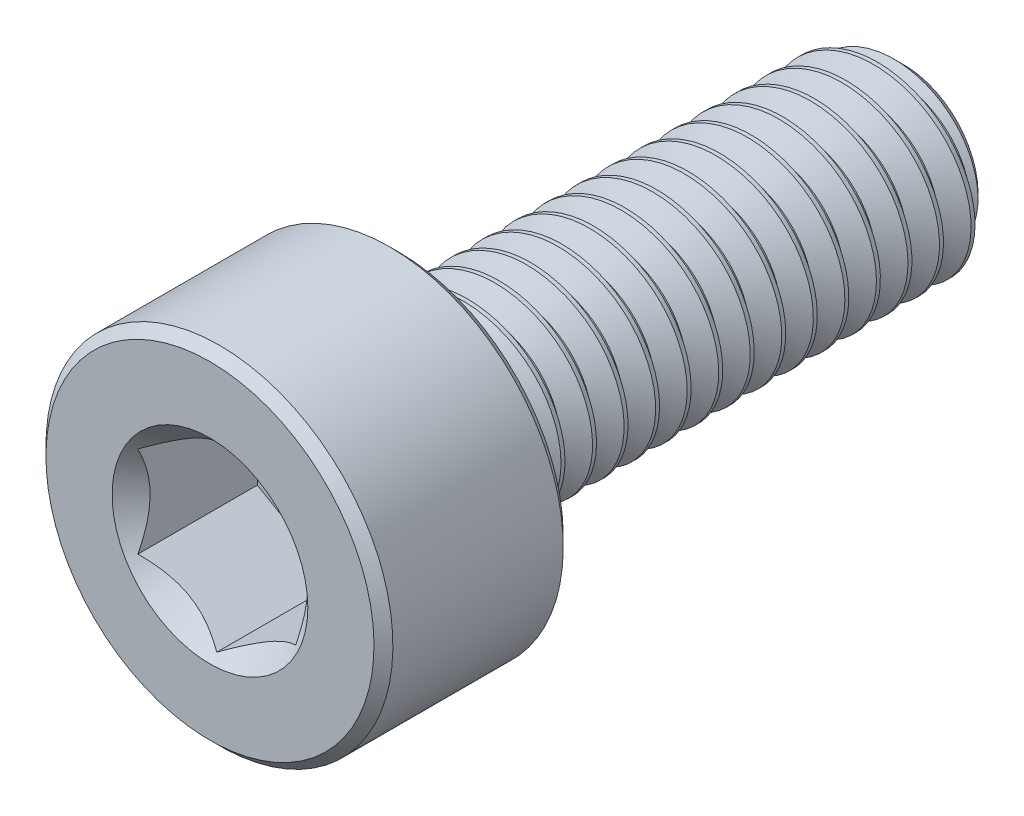
SolidWorks part; units mm, degrees
ref_plane "Front Plane" through (0, 0, 0) normal (0, 0, 1) x (1, 0, 0)
ref_plane "Top Plane" through (0, 0, 0) normal (0, 1, 0) x (1, 0, 0)
ref_plane "Right Plane" through (0, 0, 0) normal (1, 0, 0) x (0, 0, -1)
sketch "Sketch1" plane through (0, 0, 0) normal (1, 0, 0) x (0, 0, -1)
  line L0 (-5.5, 0) -> (5.5, 0) construction
  line L1 (5.5, 0) -> (5.5, 1.1752) construction
  line L2 (5.5, 1.1752) -> (5.1752, 1.5) construction
  line L3 (5.1752, 1.5) -> (5.125, 1.5) construction
  line L4 (5.125, 1.5) -> (-2.5, 1.5) construction
  line L5 (-2.5, 1.5) -> (-2.5, 2.75) construction
  line L6 (-2.5, 2.75) -> (-5.5, 2.75) construction
  line L7 (-5.5, 2.75) -> (-5.5, 0) construction
  line L8 (5.5, 1.1752) -> (5.5, 1.5) construction
  line L9 (5.4687, 1.5541) -> (5.7187, 1.1211) construction
  line L10 (5.7187, 1.1211) -> (5.9687, 1.5541) construction
  line L11 (5.9687, 1.5541) -> (5.4687, 1.5541) construction
  line L12 (5.7187, 1.5541) -> (5.7187, 1.5) construction
  line L13 (5.7187, 1.1211) -> (5.7187, 1.1752) construction
  line L14 (5.6875, 1.1752) -> (5.75, 1.1752) construction
  line L15 (5.5, 1.5) -> (5.9375, 1.5) construction
  line L16 (5.4844, 1.5271) -> (5.9531, 1.5271) construction
  line L17 (5.5, 0) -> (5.5, -1.5) construction
  line L18 (-2.65, 2.75) -> (-2.5, 2.6) construction
  line L19 (-5.35, 2.75) -> (-5.5, 2.6) construction
  line L20 (-2.5, 1.5) -> (-2.5, 0) construction
  line L21 (-2.5, 0.75) -> (0.1667, 0.75) construction
  line L22 (0.1667, 0.75) -> (2.8333, 0.75) construction
  line L23 (2.8333, 0.75) -> (5.5, 0.75) construction
  line L24 (0.1667, 0.75) -> (0.1667, 1.5) construction
  line L25 (0.1667, 1.5) -> (0.1667, 2.75) construction
  line L26 (2.8333, 0.75) -> (2.8333, 2.75) construction
  point P0 (-5.5, 1.25)
  point P3 (4.25, 1.5)
  point P4 (0, 0)
  point P18 (2.8333, 1.5)
  point P22 (5.7187, 1.1752)
  point P24 (5.125, 1.5)
  point P25 (5.7187, 1.5)
  point P28 (5.7187, 1.5271)
  point P29 (4.25, -1.5)
  point P30 (0.1667, 1.5)
  point P31 (-4, 2.75)
  point P37 (-3.025, 2.75)
  point P38 (-5.275, 2.75)
  point P45 (0.1667, 0.75)
  point P46 (2.8333, 0.75)
  dimension "D2" = 0.0625
  dimension "D7" = 0.15
  dimension "D8" = 0.15
  dimension "D9" = 0.15
  dimension "D10" = 0.075
  dimension "D11" = 0.375
  dimension "Drive Size" = 2.5
  dimension "Head Diameter" = 5.5
  dimension "Head Height" = 3
  dimension "Thread Pitch" = 0.5
  dimension "Thread Dia" = 3
  dimension "Length" = 8
  dimension "D12" = 0.375
  dimension "D4" = 1.25
  dimension "D3" = 45
sketch "Sketch2" plane through (0, 0, 0) normal (1, 0, 0) x (0, 0, -1)
  line L0 (-5.5, 0) -> (-5.5, 2.6)
  line L1 (-5.35, 2.75) -> (-2.65, 2.75)
  line L2 (-2.5, 2.6) -> (-2.5, 1.65)
  line L4 (5.1752, 1.5) -> (5.5, 1.1752)
  line L5 (5.5, 1.1752) -> (5.5, 0)
  line L6 (-2.5, 2.75) -> (-5.5, 2.75) construction
  line L7 (5.5, 0) -> (-5.5, 0)
  line L8 (-5.35, 2.75) -> (-5.5, 2.6) construction
  line L10 (-5.35, 2.75) -> (-5.5, 2.6)
  line L14 (-2.65, 2.75) -> (-2.5, 2.6) construction
  line L16 (-2.65, 2.75) -> (-2.5, 2.6)
  line L17 (-2.5, 1.5) -> (-2.5, 2.75) construction
  line L19 (-2.35, 1.5) -> (5.1752, 1.5)
  line L20 (5.125, 1.5) -> (-2.5, 1.5) construction
  arc A1 (-2.5, 1.65) -> (-2.35, 1.5) centre (-2.35, 1.65) ccw
  dimension "D3" = 0.15
revolve "Revolve1" add sketch "Sketch2" angle 360 about L7
sketch "Sketch3" plane through (0, 0, 5.5) normal (0, 0, 1) x (1, 0, 0)
  line L1 (1.25, -0.7217) -> (1.25, 0.7217)
  line L2 (1.25, 0.7217) -> (0, 1.4434)
  line L3 (0, 1.4434) -> (-1.25, 0.7217)
  line L4 (-1.25, 0.7217) -> (-1.25, -0.7217)
  line L5 (-1.25, -0.7217) -> (0, -1.4434)
  line L6 (0, -1.4434) -> (1.25, -0.7217)
  circle A0 centre (0, 0) radius 1.25 construction
  circle A1 centre (0, 0) radius 2.75 construction
  circle A2 centre (0, 0) radius 2.75 construction
  circle A3 centre (0, 0) radius 1.4434 construction
  point P13 (0, 0)
  dimension "D1" = 2.8868
extrude "Cut-Extrude1" cut sketch "Sketch3" against normal offset from surface (2 mm away) 1 up to face at (0, 2.6, 2.5)
sketch "Sketch4" plane through (0, 0, 5.5) normal (0, 0, 1) x (1, 0, 0)
  circle A0 centre (0, 0) radius 1.5516
  dimension "D1" = 3.1033
extrude "Cut-Extrude2" cut sketch "Sketch4" against normal up to vertex (1.5 mm away) draft 45 up to point (0, 2.75, 4)
sketch "Sketch11" plane through (0, 0, 0) normal (1, 0, 0) x (0, 0, -1)
  line L0 (-5.5, 0) -> (5.5, 0) construction
  line L1 (-5.5, 0) -> (5.5, 0) construction
  line L2 (-1, 0) -> (-1, 1.5) construction
  line L3 (5.125, 1.5) -> (-2.5, 1.5) construction
  line L4 (4, 0) -> (4, 1.5) construction
  line L6 (5.5, 1.1752) -> (5.5, 1.5) construction
  point P2 (-1, 0)
  point P3 (4, 0)
  dimension "D1" = 1.5
  dimension "D2" = 1.5
sketch "Sketch6" plane through (0, 0, -5.5) normal (0, 0, -1) x (-1, 0, 0)
  circle A0 centre (0, 0) radius 1.5
curve "Helix/Spiral1" pitch 0.5 height 8.5 turns 17
sketch "Sketch10" plane through (0, 0, 0) normal (1, 0, 0) x (0, 0, -1)
  line L0 (-2.35, -2.75) -> (-2.35, 2.75)
  line L5 (-5.5, 0) -> (5.5, 0) construction
  line L6 (-2.35, 1.5) -> (-2.35, -1.5) construction
  point P3 (-2.35, 0)
split "Split1" trim tools "Sketch10" bodies to split 106 resulting bodies 114 115
sketch "Sketch7" plane through (0, 0, 0) normal (1, 0, 0) x (0, 0, -1)
  line L0 (5.4844, 1.5271) -> (5.9531, 1.5271)
  line L1 (5.9531, 1.5271) -> (5.75, 1.1752)
  line L2 (5.75, 1.1752) -> (5.6875, 1.1752)
  line L3 (5.6875, 1.1752) -> (5.4844, 1.5271)
sweep "Cut-Sweep1" cut profiles "Sketch7" path "Helix/Spiral1" align with end faces yes
sketch "Sketch8" plane through (0, 0, 0) normal (1, 0, 0) x (0, 0, -1)
  line L0 (-2.5, 0) -> (-2.5, 1.5)
  line L1 (-2.35, -1.5) -> (-2.35, 1.5) construction
  line L2 (-2.5, 1.5) -> (-2.35, 1.5)
  line L4 (-2.35, 1.5) -> (-1.484, 0)
  line L5 (-1.484, 0) -> (-2.5, 0)
  line L6 (5.125, 1.5) -> (-2.5, 1.5) construction
  line L7 (-5.5, 0) -> (5.5, 0) construction
  dimension "D1" = 60
revolve "Revolve2" add sketch "Sketch8" angle 360 about L5
equation "\"D2@Sketch1\" = \"Thread Pitch@Sketch1\" / 8"
equation "\"D4@Helix/Spiral1\" = \"Thread Pitch@Sketch1\""
equation "\"D7@Sketch1\" = \"Head Height@Sketch1\" * .05"
equation "\"D8@Sketch1\"=\"D7@Sketch1\""
equation "\"D9@Sketch1\"=\"D7@Sketch1\""
equation "\"D10@Sketch1\"=\"D7@Sketch1\"/2"
equation "\"D11@Sketch1\"=\"D10@Sketch1\"*5"
equation "\"D4@Sketch1\"=\"Thread Pitch@Sketch1\"*2.5"
equation "\"D12@Sketch1\"=\"Thread Pitch@Sketch1\"*.75"
equation "\"D3@Helix/Spiral1\"=\"Length@Sketch1\"+\"Thread Pitch@Sketch1\""
equation "\"D3@Sketch2\"=\"Thread Dia@Sketch1\"*0.05"
equation "\"D1@Sketch11\"=\"Length@Sketch1\"*0.1875"
equation "\"D2@Sketch11\"=\"D1@Sketch11\""
equation "\"D1@Sketch4\"=\"D1@Sketch3\"*1.075"
